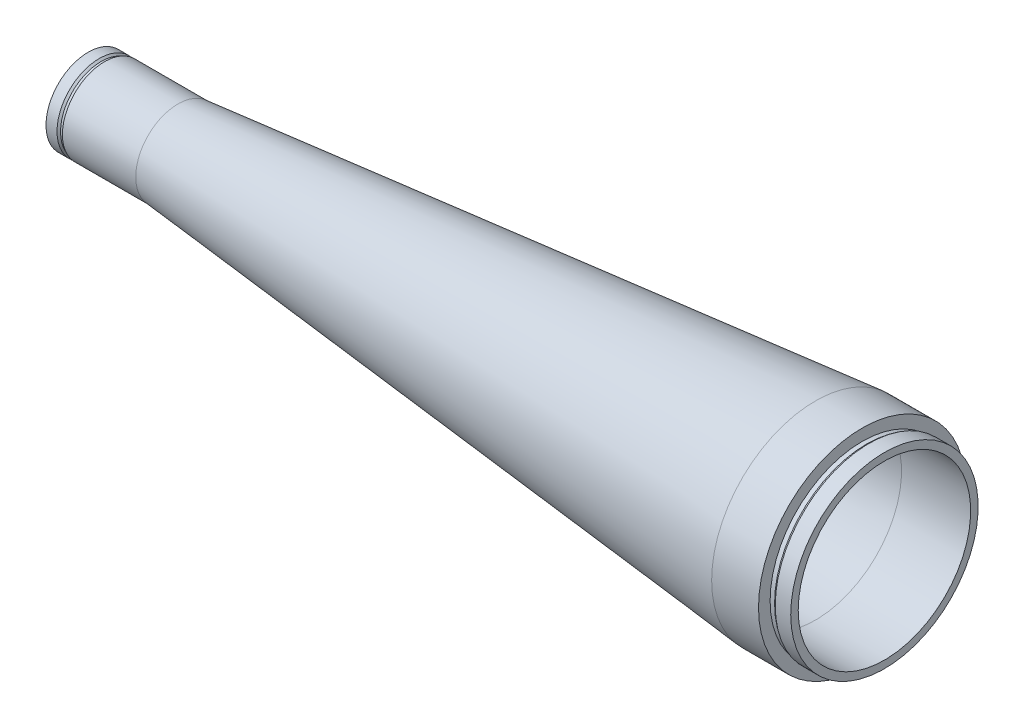
SolidWorks part; units mm, degrees
material "2018 slitina"
ref_plane "Přední rovina" through (0, 0, 0) normal (0, 0, 1) x (1, 0, 0)
ref_plane "Horní rovina" through (0, 0, 0) normal (0, 1, 0) x (1, 0, 0)
ref_plane "Pravá rovina" through (0, 0, 0) normal (1, 0, 0) x (0, 0, -1)
sketch "Skica1" plane through (0, 0, 0) normal (0, 0, 1) x (1, 0, 0)
  line L0 (-36.7133, 44.25) -> (-36.7133, -44.25) construction
  line L1 (-36.7133, 44.25) -> (-36.7133, -38.9168) construction
  line L2 (-172.4424, 0) -> (-98.619, 0) construction
  line L3 (-36.7133, -44.25) -> (-56.7133, -44.25)
  line L7 (-322.05, -12.9) -> (-217.05, -23.4)
  line L9 (-212.6322, -25.6) -> (-117.05, -29.4)
  line L10 (-117.05, -29.4) -> (-117.05, -33.4)
  line L12 (-56.7133, -36.8) -> (-27.2133, -36.8)
  line L13 (-27.2133, -36.8) -> (-27.2133, -40)
  line L14 (-27.2133, -40) -> (-33.8133, -40)
  line L15 (-36.7133, -39.3) -> (-36.7133, -44.25)
  line L16 (-26.7133, 38.094) -> (-26.7133, -38.094) construction
  line L17 (-56.7133, -44.25) -> (-56.7133, -36.8) construction
  line L19 (-34.8133, -39.3) -> (-36.7133, -39.3)
  line L21 (-34.8133, -39.3) -> (-33.8133, -40)
  line L22 (-506.9511, 0) -> (-119.3909, 0) construction
  line L23 (-115.55, -33.4) -> (-117.05, -33.4)
  line L24 (-117.05, 27.4) -> (-117.05, -27.4) construction
  line L27 (-112.0997, -33.4124) -> (-56.7133, -36.8)
  line L28 (-217.05, -19.7) -> (-217.05, 19.7) construction
  line L29 (-117.05, -27.4) -> (-115.05, -29.4) construction
  line L34 (-115.05, -33.4) -> (-117.05, -33.4) construction
  line L35 (-115.05, -33.4) -> (-115.05, -29.4) construction
  line L37 (-117.05, -33.4) -> (-117.05, -27.4) construction
  line L40 (-115.55, -33.4) -> (-115.55, -34.5)
  line L41 (-115.55, -34.5) -> (-113.1873, -34.5)
  line L42 (-113.1873, -34.5) -> (-112.0997, -33.4124)
  line L43 (-113.45, -34.1) -> (-113.45, -30.9) construction
  line L44 (-36.7133, -39.3) -> (-36.7133, -44.25) construction
  line L45 (-217.05, -23.4) -> (-217.05, -25.4)
  line L46 (-217.05, -25.4) -> (-215.55, -25.4)
  line L47 (-215.55, -25.4) -> (-215.55, -26.9)
  line L48 (-215.55, -26.9) -> (-213.9322, -26.9)
  line L49 (-213.9322, -26.9) -> (-212.6322, -25.6)
  line L50 (-217.05, -25.4) -> (-215.05, -25.4) construction
  line L51 (-215.05, -25.4) -> (-215.05, -21.7) construction
  line L52 (-215.05, -21.7) -> (-217.05, -19.7) construction
  line L53 (-217.05, -19.7) -> (-217.05, -25.4) construction
  line L54 (-213.8, -26.25) -> (-213.8, -23.75) construction
  line L55 (-367.05, -18) -> (-362.35, -18)
  line L56 (-328.75, -18) -> (-56.7133, -44.25)
  line L57 (-322.05, -9.65) -> (-322.05, 9.65) construction
  line L59 (-322.05, -12.9) -> (-322.05, -15.4)
  line L60 (-322.05, -15.4) -> (-323.75, -15.4)
  line L61 (-323.75, -15.4) -> (-323.75, -16.5)
  line L62 (-323.75, -16.5) -> (-324.9642, -16.5)
  line L63 (-324.9642, -16.5) -> (-325.9642, -15.5)
  line L64 (-325.9642, -15.5) -> (-345.05, -15.5)
  line L65 (-322.05, -15.4) -> (-322.05, -9.65) construction
  line L66 (-322.05, -9.65) -> (-324.05, -11.65) construction
  line L67 (-324.05, -11.65) -> (-324.05, -15.4) construction
  line L68 (-324.05, -15.4) -> (-322.05, -15.4) construction
  line L69 (-325.05, -16) -> (-325.05, -14) construction
  line L70 (-325.05, -15) -> (-325.9642, -15.5) construction
  line L71 (-367.05, 6) -> (-367.05, -6) construction
  line L72 (-367.05, -15.5) -> (-367.05, -18)
  line L75 (-345.05, -15.5) -> (-367.05, -15.5)
  line L76 (-360.05, -18) -> (-360.05, -17.3)
  line L77 (-360.05, -17.3) -> (-361.55, -17.3)
  line L78 (-361.55, -17.3) -> (-362.35, -18)
  line L79 (-360.05, -18) -> (-328.75, -18)
  arc A0 (-15.7133, 37.5) -> (-15.7133, -37.5) centre (509.65, 0) ccw construction
  arc A1 (-15.7133, 37.5) -> (-15.7133, -37.5) centre (509.65, 0) ccw construction
  circle A3 centre (-213.8, -25) radius 1.25 construction
  circle A4 centre (-113.45, -32.5) radius 1.6 construction
  circle A5 centre (-325.05, -15) radius 1 construction
  point P28 (-17.05, 0)
  point P31 (-217.05, 0)
  point P32 (-117.05, 0)
  point P55 (-322.05, 0)
  point P69 (-367.05, 0)
  dimension "D7" = 100
  dimension "D17" = 3.5
  dimension "D9" = 68.2
  dimension "D12" = 3.2
  dimension "D18" = 69
  dimension "D24" = 2.5
  dimension "D37" = 2
  dimension "D1" = 0.5
  dimension "D2" = 80
  dimension "D3" = 0.7
  dimension "D4" = 1.9
  dimension "D5" = 2.9
  dimension "D6" = 2.5
  dimension "D8" = 2
  dimension "D10" = 4
  dimension "D11" = 54.8
  dimension "D13" = 39.4
  dimension "D14" = 45
  dimension "D15" = 20
  dimension "D16" = 100
  dimension "D19" = 2
  dimension "D20" = 45
  dimension "D21" = 0.5
  dimension "D22" = 0.0124
  dimension "D23" = 52.5
  dimension "D25" = 45
  dimension "D26" = 45
  dimension "D27" = 2
  dimension "D28" = 0.2
  dimension "D29" = 1.5
  dimension "D30" = 2
  dimension "D31" = 53.8
  dimension "D32" = 0.5
  dimension "D33" = 36
  dimension "D34" = 105
  dimension "D35" = 19.3
  dimension "D36" = 31
  dimension "D38" = 45
  dimension "D39" = 2
  dimension "D40" = 32
  dimension "D41" = 0.3
  dimension "D42" = 0.1
  dimension "D43" = 5
  dimension "D44" = 2.5
  dimension "D45" = 33
  dimension "D46" = 45
  dimension "D47" = 350
  dimension "D48" = 12
  dimension "D49" = 1.5
  dimension "D50" = 2.3
  dimension "D51" = 0.7
  dimension "D52" = 7
revolve "Rotovat1" add sketch "Skica1" angle 360 about L2
cosmetic thread "Kosmetický závit2" parameters "D2"=35
